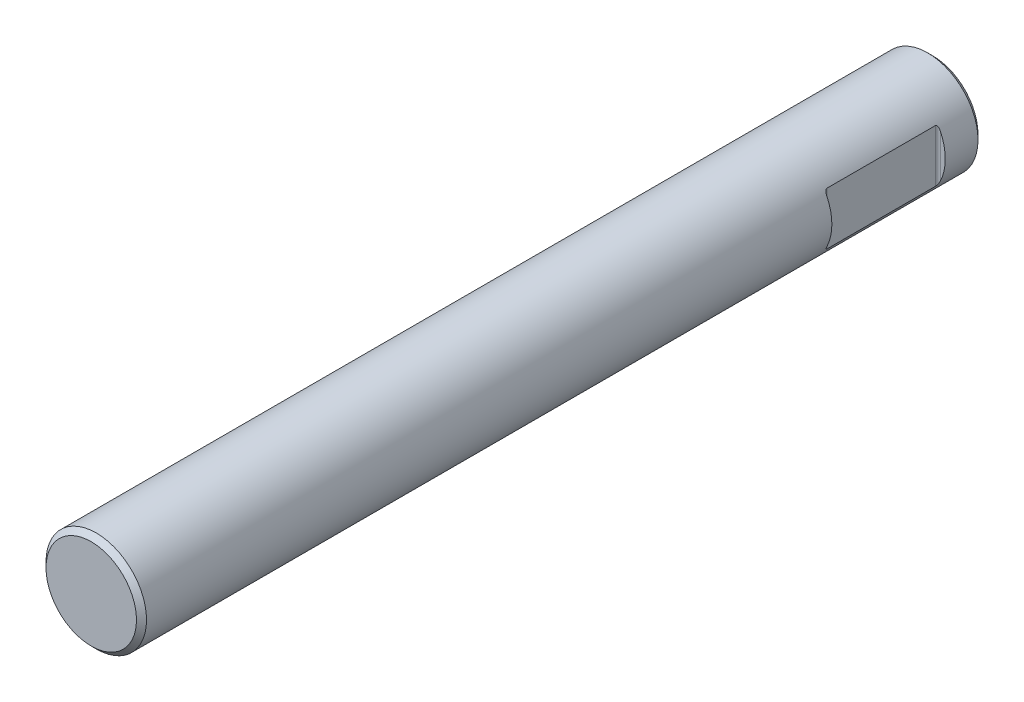
SolidWorks part; units mm, degrees
material "1.4000 (X6Cr13)"
ref_plane "Ebene vorne" through (0, 0, 0) normal (0, 0, 1) x (1, 0, 0)
ref_plane "Ebene oben" through (0, 0, 0) normal (0, 1, 0) x (1, 0, 0)
ref_plane "Ebene rechts" through (0, 0, 0) normal (1, 0, 0) x (0, 0, -1)
sketch "Skizze1" plane through (0, 0, 0) normal (1, 0, 0) x (0, 0, -1)
  line L0 (-50.5169, 0) -> (54.2703, 0) construction
  line L1 (0, 19.5371) -> (0, -16.0786) construction
  line L2 (0, 0) -> (0, 1.995)
  line L4 (33.4, 1.995) -> (33.4, 0)
  line L5 (33.4, 0) -> (0, 0)
  line L9 (0, 1.995) -> (33.4, 1.995)
  dimension "D1" = 3.99
  dimension "D2" = 33.4
revolve "Rotation1" add sketch "Skizze1" angle 360 about L0
ref_axis "Achse1" through (0, 0, 1.67) along (0, 0, -1)
chamfer "Fase1" distance 0.2 angle 45 2 edges at (1.995, 0, -33.4) (1.995, 0, 0)
sketch "Skizze2" plane through (0, 0, 0) normal (0, 1, 0) x (1, 0, 0)
  line L0 (1.795, 33.4) -> (-1.795, 33.4) construction
  line L7 (-6.2, 27.4) -> (-1.8, 27.4)
  line L8 (-6.2, 27.4) -> (-6.2, 31.9)
  line L9 (-6.2, 31.9) -> (-1.8, 31.9)
  line L10 (-1.7, 27.5) -> (-1.7, 31.8)
  line L11 (-6.2, 27.4) -> (-1.7, 31.9) construction
  line L12 (-6.2, 31.9) -> (-1.7, 27.4) construction
  line L13 (0, -7.285) -> (0, 53.978) construction
  line L14 (-1.995, 40.456) -> (-1.995, -1.4737) construction
  line L15 (-1.995, 33.2) -> (-1.995, 0.2) construction
  line L16 (6.2, 31.9) -> (1.7, 27.4) construction
  line L17 (6.2, 27.4) -> (1.7, 31.9) construction
  line L20 (1.7, 27.5) -> (1.7, 31.8)
  line L21 (6.2, 31.9) -> (1.8, 31.9)
  line L22 (6.2, 27.4) -> (6.2, 31.9)
  line L23 (6.2, 27.4) -> (1.8, 27.4)
  arc A0 (1.7, 31.8) -> (1.8, 31.9) centre (1.8, 31.8) cw
  arc A1 (1.8, 27.4) -> (1.7, 27.5) centre (1.8, 27.5) cw
  arc A6 (-1.8, 27.4) -> (-1.7, 27.5) centre (-1.8, 27.5) ccw
  arc A7 (-1.7, 31.8) -> (-1.8, 31.9) centre (-1.8, 31.8) ccw
  point P5 (-3.95, 29.65)
  point P19 (-1.7293, 31.8707)
  point P20 (-1.7293, 27.4293)
  point P57 (1.7293, 27.4293)
  point P58 (1.7293, 31.8707)
  point P59 (3.95, 29.65)
  dimension "D2" = 0.1
  dimension "D1" = 3.4
  dimension "D3" = 4.5
  dimension "D4" = 1.5
  dimension "D7" = 4.3
extrude "Schnitt-Linear austragen1" cut sketch "Skizze2" against normal through all and the other way through all
